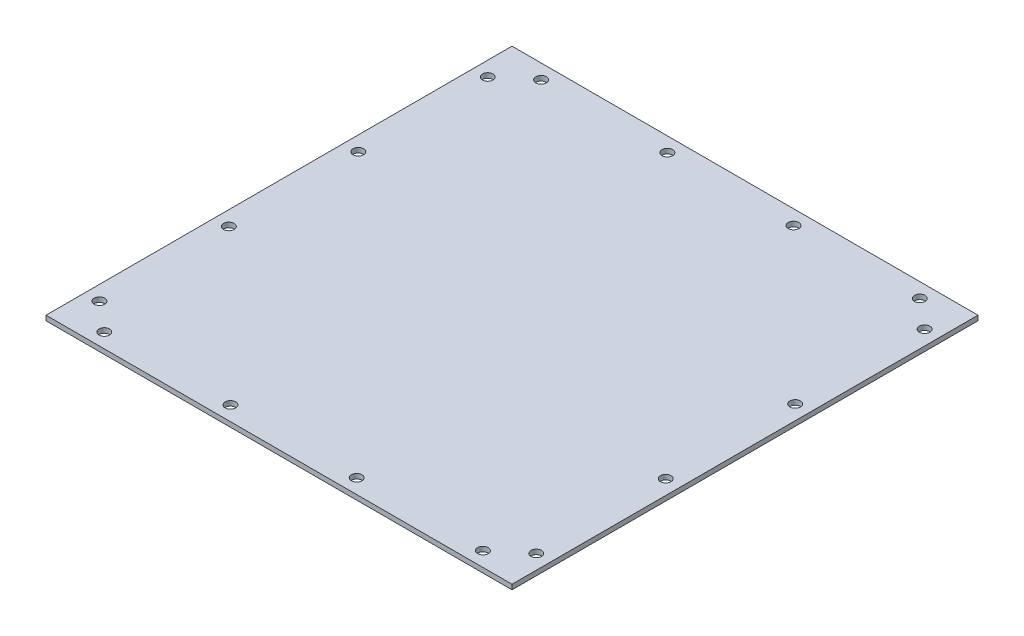
SolidWorks part; units mm, degrees
ref_plane "Front Plane" through (0, 0, 0) normal (0, 0, 1) x (1, 0, 0)
ref_plane "Top Plane" through (0, 0, 0) normal (0, 1, 0) x (1, 0, 0)
ref_plane "Right Plane" through (0, 0, 0) normal (1, 0, 0) x (0, 0, -1)
sketch "Sketch2" plane through (0, 0, 0) normal (0, 1, 0) x (1, 0, 0)
  line L0 (0, 0) -> (152.4, 0)
  line L1 (152.4, 0) -> (152.4, 152.4)
  line L2 (152.4, 152.4) -> (0, 152.4)
  line L3 (0, 152.4) -> (0, 0)
  dimension "D1" = 152.4
  dimension "D2" = 152.4
extrude "Boss-Extrude1" add sketch "Sketch2" along normal blind 1.5875
sketch "Sketch3" plane through (0, 1.5875, 0) normal (0, 1, 0) x (1, 0, 0)
  line L0 (0, 152.4) -> (4.7625, 152.4)
  line L1 (152.4, 152.4) -> (0, 152.4) construction
  line L2 (4.7625, 152.4) -> (4.7625, 0)
  line L3 (0, 0) -> (152.4, 0) construction
  line L4 (0, 152.4) -> (0, 147.6375)
  line L5 (0, 152.4) -> (0, 0) construction
  line L6 (0, 147.6375) -> (152.4, 147.6375)
  line L7 (152.4, 0) -> (152.4, 152.4) construction
  line L8 (152.4, 152.4) -> (147.6375, 152.4)
  line L9 (147.6375, 152.4) -> (147.6375, 0)
  line L10 (152.4, 0) -> (152.4, 4.7625)
  line L11 (152.4, 4.7625) -> (0, 4.7625)
  point P21 (4.7625, 139.7)
  point P23 (14.2875, 147.6375)
  point P24 (147.6375, 139.7)
  point P25 (138.1125, 4.7625)
  point P26 (4.7625, 12.7)
  dimension "D1" = 4.7625
  dimension "D2" = 4.7625
  dimension "D3" = 4.7625
  dimension "D4" = 4.7625
  dimension "D5" = 12.7
  dimension "D6" = 14.2875
  dimension "D7" = 12.7
  dimension "D8" = 14.2875
  dimension "D9" = 12.7
sketch "Sketch4" plane through (0, 1.5875, 0) normal (0, 1, 0) x (1, 0, 0)
  point P0 (14.2875, 147.6375)
  point P3 (147.6375, 139.7)
  point P6 (138.1125, 4.7625)
  point P9 (4.7625, 12.7)
sketch "Sketch6" plane through (0, 1.5875, 0) normal (0, 1, 0) x (1, 0, 0)
  line L0 (152.4, 4.7625) -> (0, 4.7625) construction
  line L1 (0, 152.4) -> (0, 0) construction
  point P0 (14.2875, 147.6375)
  point P3 (14.2875, 4.7625)
  dimension "D1" = 14.2875
hole_wizard "#5 Clearance Hole2" positions "Sketch6" profile "Sketch7" hole size "#5" standard "ANSI Inch" end condition through all
sketch "Sketch7" plane through (14.2875, 1.5875, -147.6375) normal (1, 0, 0) x (0, 0, 1)
  line L0 (0, 0) -> (0, 1.5875)
  line L1 (0, 1.5875) -> (1.7272, 1.5875)
  line L2 (1.7272, 1.5875) -> (1.7272, 0)
  line L5 (1.7272, 0) -> (0, 0)
  line L11 (0, -6.35) -> (0, 107.95) construction
  dimension "Thru Hole Dia." = 3.4544
  dimension "Thru Hole Depth" = 1.5875
sketch "Sketch8" plane through (0, 1.5875, 0) normal (0, 1, 0) x (1, 0, 0)
  point P0 (4.7625, 139.7)
  point P3 (147.6375, 139.7)
hole_wizard "#5 Clearance Hole3" positions "Sketch8" profile "Sketch9" hole size "#5" standard "ANSI Inch" end condition through all
sketch "Sketch9" plane through (4.7625, 1.5875, -139.7) normal (1, 0, 0) x (0, 0, 1)
  line L0 (0, 0) -> (0, 1.5875)
  line L1 (0, 1.5875) -> (1.7272, 1.5875)
  line L2 (1.7272, 1.5875) -> (1.7272, 0)
  line L5 (1.7272, 0) -> (0, 0)
  line L11 (0, -6.35) -> (0, 107.95) construction
  dimension "Thru Hole Dia." = 3.4544
  dimension "Thru Hole Depth" = 1.5875
pattern_linear "LPattern1" count 4 spacing 42.3333 along (0, 0, 1) of "#5 Clearance Hole3"
pattern_linear "LPattern2" count 4 spacing 41.275 along (1, 0, 0) of "#5 Clearance Hole2"
